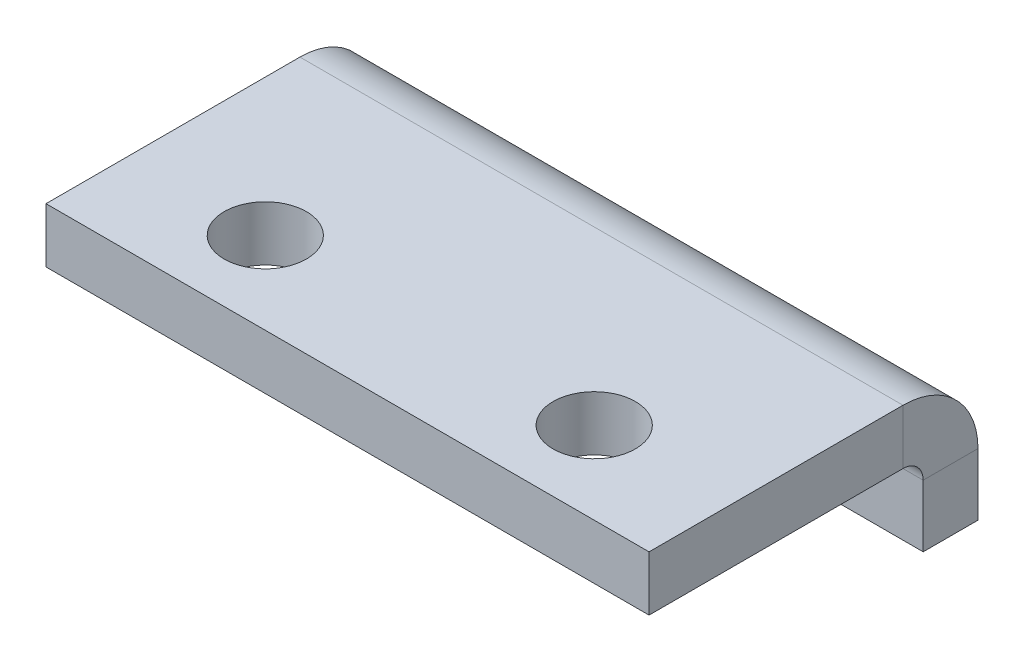
SolidWorks part; units mm, degrees
note: The reader was unsure of these and kept them because the rebuilt part matched: flange length of "Edge-Flange1".
ref_plane "Front Plane" through (0, 0, 0) normal (0, 0, 1) x (1, 0, 0)
ref_plane "Top Plane" through (0, 0, 0) normal (0, 1, 0) x (1, 0, 0)
ref_plane "Right Plane" through (0, 0, 0) normal (1, 0, 0) x (0, 0, -1)
sketch "Sketch1" plane through (0, 0, 0) normal (1, 0, 0) x (0, 0, -1)
  line L0 (0, 0) -> (12, 0)
  dimension "D1" = 12
sheet metal parameters "Sheet-Metal1" thickness 2 parameters "D1"=0.7366
base flange "Base-Flange1" sketch "Sketch1" end condition mid plane depth 22 reverse direction no thickness 2 reverse thickness direction no bend radius 0.7366
sketch "Sketch2" plane through (0, 0, 0) normal (0, 1, 0) x (1, 0, 0)
  line L0 (-6, 3) -> (6, 3) construction
  line L1 (11, 0) -> (-11, 0) construction
  circle A0 centre (-6, 3) radius 1.5
  circle A1 centre (6, 3) radius 1.5
  point P4 (0, 3)
  dimension "D3" = 3
  dimension "D1" = 3
  dimension "D2" = 12
extrude "Cut-Extrude1" cut sketch "Sketch2" against normal blind 10 normal cut yes
edge flange "Edge-Flange1" sketch "Sketch5" flange angle 90 flange length 5 flange position material inside bend radius 0.7366 thickness 2 relief rectangular parameters "D6"=10
sketch "Sketch5" plane through (0, -2, -12) normal (0, 0, 1) x (-1, 0, 0)
  line L2 (-11, 0) -> (-11, 3)
  line L3 (-11, 3) -> (11, 3)
  line L4 (11, 3) -> (11, 0)
  line L5 (11, 0) -> (-11, 0) construction
  line L6 (11, 0) -> (-11, 0)
bend "EdgeBend1" bend radius 0.7366 bend angle 90 parameters "D5"=1
flat pattern "Flat-Pattern1" [suppressed]
sketch "Bend-Lines1" plane through (0, 0, 0) normal (0, 1, 0) x (-1, 0, 0)
  point P0 (0, -24.02)
  point P1 (-20, -24.02)
sketch3d "Bounding-Box1" [suppressed]
  line L0 (20, -35.04, 0) -> (20, 0, 0) construction
  line L1 (0, -35.04, 0) -> (0, 0, 0) construction
  line L2 (20, -35.04, 0) -> (0, -35.04, 0) construction
  line L3 (20, 0, 0) -> (0, 0, 0) construction
bend of the flat pattern "Flatten-<EdgeBend1>1"
